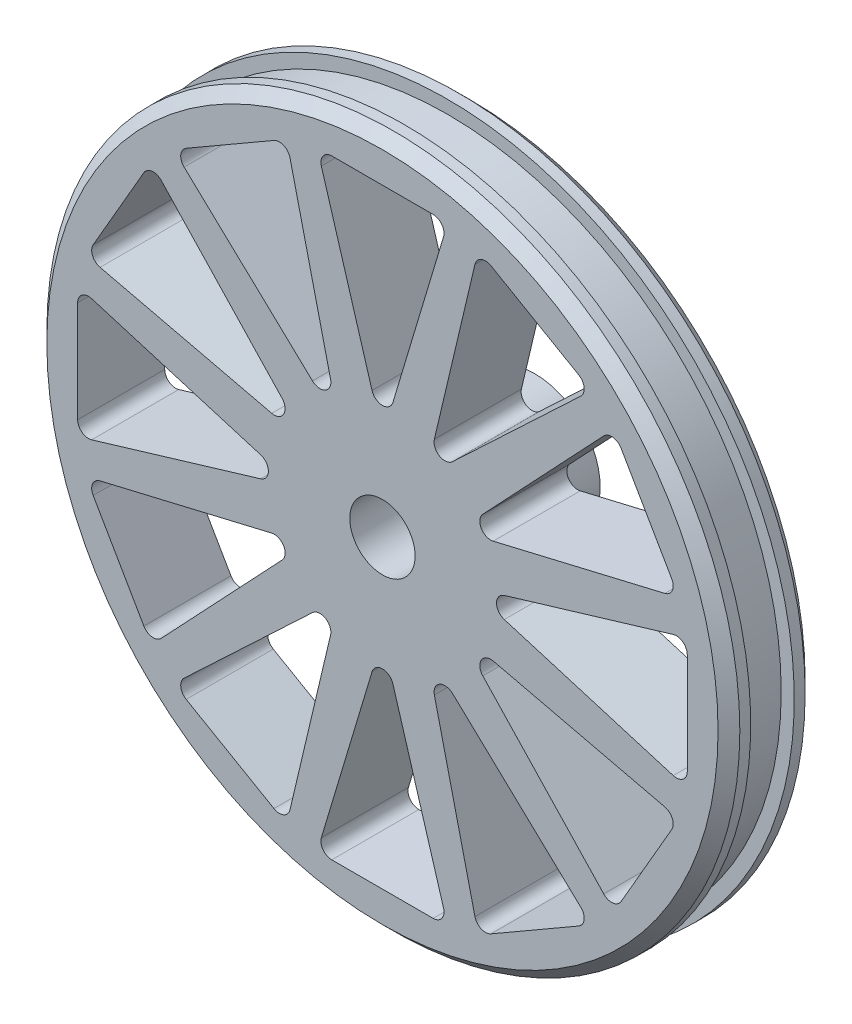
SolidWorks part; units mm, degrees
ref_plane "前视基准面" through (0, 0, 0) normal (0, 0, 1) x (1, 0, 0)
ref_plane "上视基准面" through (0, 0, 0) normal (0, 1, 0) x (1, 0, 0)
ref_plane "右视基准面" through (0, 0, 0) normal (1, 0, 0) x (0, 0, -1)
sketch "草图1" plane through (0, 0, 0) normal (0, 0, 1) x (1, 0, 0)
  circle A0 centre (0, 0) radius 1.5
  circle A3 centre (0, 0) radius 15.9155
  dimension "D1" = 3
  dimension "D3" = 31.831
extrude "凸台-拉伸1" add sketch "草图1" along normal blind 4
sketch "草图3" plane through (0, 0, 0) normal (0, 0, -1) x (-1, 0, 0)
  circle A0 centre (0, 0) radius 1.5
  circle A1 centre (0, 0) radius 3
  dimension "D1" = 1.5
extrude "凸台-拉伸2" add sketch "草图3" along normal blind 3
sketch "草图4" plane through (0, 0, 0) normal (1, 0, 0) x (0, 0, -1)
  line L0 (3, -3) -> (3, 3) construction
  circle A0 centre (1.5, 0) radius 1
  dimension "D1" = 2
  dimension "D2" = 1.5
extrude "切除-拉伸3" cut sketch "草图4" against normal blind 4
chamfer "倒角1" distance 0.5 angle 45 1 edges at (-1.5, 0, -3)
sketch "草图6" plane through (0, 0, 0) normal (0, 0, -1) x (-1, 0, 0)
  circle A0 centre (0, 0) radius 15.3155
  circle A1 centre (0, 0) radius 15.9155 construction
  circle A2 centre (0, 0) radius 25.5937
  dimension "D1" = 0.6
extrude "切除-拉伸5" cut sketch "草图6" against normal blind 2 from offset 1 offset against normal yes
chamfer "倒角3" distance 0.5 angle 45 2 edges at (15.9155, 0, 4) (15.9155, 0, 0)
sketch "草图7" plane through (0, 0, 0) normal (0, 0, -1) x (-1, 0, 0)
  line L0 (-4, 0) -> (0, 0) construction
  line L1 (-5.5964, 0.4789) -> (-13.3563, 2.8069)
  line L2 (-14, 2.328) -> (-14, -2.328)
  line L3 (-5.5964, -0.4789) -> (-13.3563, -2.8069)
  line L4 (-10.9604, 9.0161) -> (-13.2883, 4.9839)
  line L5 (-5.0861, 2.3834) -> (-12.9704, 4.2473)
  line L6 (-4.6071, 3.2129) -> (-10.1635, 9.109)
  line L7 (-4.9839, 13.2883) -> (-9.0161, 10.9604)
  line L8 (-3.2129, 4.6071) -> (-9.109, 10.1635)
  line L9 (-2.3834, 5.0861) -> (-4.2473, 12.9704)
  line L10 (2.328, 14) -> (-2.328, 14)
  line L11 (-0.4789, 5.5964) -> (-2.8069, 13.3563)
  line L12 (0.4789, 5.5964) -> (2.8069, 13.3563)
  line L13 (9.0161, 10.9604) -> (4.9839, 13.2883)
  line L14 (2.3834, 5.0861) -> (4.2473, 12.9704)
  line L15 (3.2129, 4.6071) -> (9.109, 10.1635)
  line L16 (13.2883, 4.9839) -> (10.9604, 9.0161)
  line L17 (4.6071, 3.2129) -> (10.1635, 9.109)
  line L18 (5.0861, 2.3834) -> (12.9704, 4.2473)
  line L19 (14, -2.328) -> (14, 2.328)
  line L20 (5.5964, 0.4789) -> (13.3563, 2.8069)
  line L21 (5.5964, -0.4789) -> (13.3563, -2.8069)
  line L22 (10.9604, -9.0161) -> (13.2883, -4.9839)
  line L23 (5.0861, -2.3834) -> (12.9704, -4.2473)
  line L24 (4.6071, -3.2129) -> (10.1635, -9.109)
  line L25 (4.9839, -13.2883) -> (9.0161, -10.9604)
  line L26 (3.2129, -4.6071) -> (9.109, -10.1635)
  line L27 (2.3834, -5.0861) -> (4.2473, -12.9704)
  line L28 (-2.328, -14) -> (2.328, -14)
  line L29 (0.4789, -5.5964) -> (2.8069, -13.3563)
  line L30 (-0.4789, -5.5964) -> (-2.8069, -13.3563)
  line L31 (-9.0161, -10.9604) -> (-4.9839, -13.2883)
  line L32 (-2.3834, -5.0861) -> (-4.2473, -12.9704)
  line L33 (-3.2129, -4.6071) -> (-9.109, -10.1635)
  line L34 (-13.2883, -4.9839) -> (-10.9604, -9.0161)
  line L35 (-4.6071, -3.2129) -> (-10.1635, -9.109)
  line L36 (-5.0861, -2.3834) -> (-12.9704, -4.2473)
  arc A0 (-13.3563, -2.8069) -> (-14, -2.328) centre (-13.5, -2.328) cw
  arc A1 (-5.5964, -0.4789) -> (-5.5964, 0.4789) centre (-5.7401, 0) ccw
  arc A2 (-14, 2.328) -> (-13.3563, 2.8069) centre (-13.5, 2.328) cw
  arc A3 (-10.9604, 9.0161) -> (-10.1635, 9.109) centre (-10.5274, 8.7661) cw
  arc A4 (-12.9704, 4.2473) -> (-13.2883, 4.9839) centre (-12.8553, 4.7339) cw
  arc A5 (-5.0861, 2.3834) -> (-4.6071, 3.2129) centre (-4.971, 2.87) ccw
  arc A6 (-4.9839, 13.2883) -> (-4.2473, 12.9704) centre (-4.7339, 12.8553) cw
  arc A7 (-9.109, 10.1635) -> (-9.0161, 10.9604) centre (-8.7661, 10.5274) cw
  arc A8 (-3.2129, 4.6071) -> (-2.3834, 5.0861) centre (-2.87, 4.971) ccw
  arc A9 (2.328, 14) -> (2.8069, 13.3563) centre (2.328, 13.5) cw
  arc A10 (-2.8069, 13.3563) -> (-2.328, 14) centre (-2.328, 13.5) cw
  arc A11 (-0.4789, 5.5964) -> (0.4789, 5.5964) centre (0, 5.7401) ccw
  arc A12 (9.0161, 10.9604) -> (9.109, 10.1635) centre (8.7661, 10.5274) cw
  arc A13 (4.2473, 12.9704) -> (4.9839, 13.2883) centre (4.7339, 12.8553) cw
  arc A14 (2.3834, 5.0861) -> (3.2129, 4.6071) centre (2.87, 4.971) ccw
  arc A15 (13.2883, 4.9839) -> (12.9704, 4.2473) centre (12.8553, 4.7339) cw
  arc A16 (10.1635, 9.109) -> (10.9604, 9.0161) centre (10.5274, 8.7661) cw
  arc A17 (4.6071, 3.2129) -> (5.0861, 2.3834) centre (4.971, 2.87) ccw
  arc A18 (14, -2.328) -> (13.3563, -2.8069) centre (13.5, -2.328) cw
  arc A19 (13.3563, 2.8069) -> (14, 2.328) centre (13.5, 2.328) cw
  arc A20 (5.5964, 0.4789) -> (5.5964, -0.4789) centre (5.7401, 0) ccw
  arc A21 (10.9604, -9.0161) -> (10.1635, -9.109) centre (10.5274, -8.7661) cw
  arc A22 (12.9704, -4.2473) -> (13.2883, -4.9839) centre (12.8553, -4.7339) cw
  arc A23 (5.0861, -2.3834) -> (4.6071, -3.2129) centre (4.971, -2.87) ccw
  arc A24 (4.9839, -13.2883) -> (4.2473, -12.9704) centre (4.7339, -12.8553) cw
  arc A25 (9.109, -10.1635) -> (9.0161, -10.9604) centre (8.7661, -10.5274) cw
  arc A26 (3.2129, -4.6071) -> (2.3834, -5.0861) centre (2.87, -4.971) ccw
  arc A27 (-2.328, -14) -> (-2.8069, -13.3563) centre (-2.328, -13.5) cw
  arc A28 (2.8069, -13.3563) -> (2.328, -14) centre (2.328, -13.5) cw
  arc A29 (0.4789, -5.5964) -> (-0.4789, -5.5964) centre (0, -5.7401) ccw
  arc A30 (-9.0161, -10.9604) -> (-9.109, -10.1635) centre (-8.7661, -10.5274) cw
  arc A31 (-4.2473, -12.9704) -> (-4.9839, -13.2883) centre (-4.7339, -12.8553) cw
  arc A32 (-2.3834, -5.0861) -> (-3.2129, -4.6071) centre (-2.87, -4.971) ccw
  arc A33 (-13.2883, -4.9839) -> (-12.9704, -4.2473) centre (-12.8553, -4.7339) cw
  arc A34 (-10.1635, -9.109) -> (-10.9604, -9.0161) centre (-10.5274, -8.7661) cw
  arc A35 (-4.6071, -3.2129) -> (-5.0861, -2.3834) centre (-4.971, -2.87) ccw
  point P8 (-14, 0)
  point P10 (-14, -3)
  point P16 (-14, 3)
  point P116 (0, 0)
  dimension "D4" = 0.5
  dimension "D1" = 3
  dimension "D2" = 10
  dimension "D3" = 4
  dimension "D5" = 12
extrude "切除-拉伸6" cut sketch "草图7" against normal blind 9
sketch "草图8" plane through (0, 0, 4) normal (0, 0, 1) x (1, 0, 0)
  circle A1 centre (0, 0) radius 4.5
  dimension "D2" = 9
extrude "凸台-拉伸3" add sketch "草图8" along normal blind 1
sketch "草图9" plane through (0, 0, 5) normal (0, 0, 1) x (1, 0, 0)
  line L0 (-3, 0) -> (-3, -3.3541)
  line L1 (3, 0) -> (3, -3.3541)
  arc A0 (3, 0) -> (-3, 0) centre (0, 0) ccw
  arc A1 (3, -3.3541) -> (-3, -3.3541) centre (0, 0) ccw
  dimension "D1" = 6
extrude "凸台-拉伸4" add sketch "草图9" along normal blind 3
sketch "草图10" plane through (0, 0, 8) normal (0, 0, 1) x (1, 0, 0)
  circle A0 centre (0, 0) radius 4.5
  circle A1 centre (0, 0) radius 1.55
  dimension "D1" = 3.1
extrude "凸台-拉伸5" add sketch "草图10" against normal blind 0.4 and the other way blind 1.6
chamfer "倒角4" distance 0.5 angle 45 1 edges at (4.5, 0, 9.6)
sketch "草图11" plane through (0, 0, 4) normal (0, 0, 1) x (1, 0, 0)
  circle A0 centre (0, 0) radius 5.5606
extrude "切除-拉伸7" cut sketch "草图11" along normal blind 7
